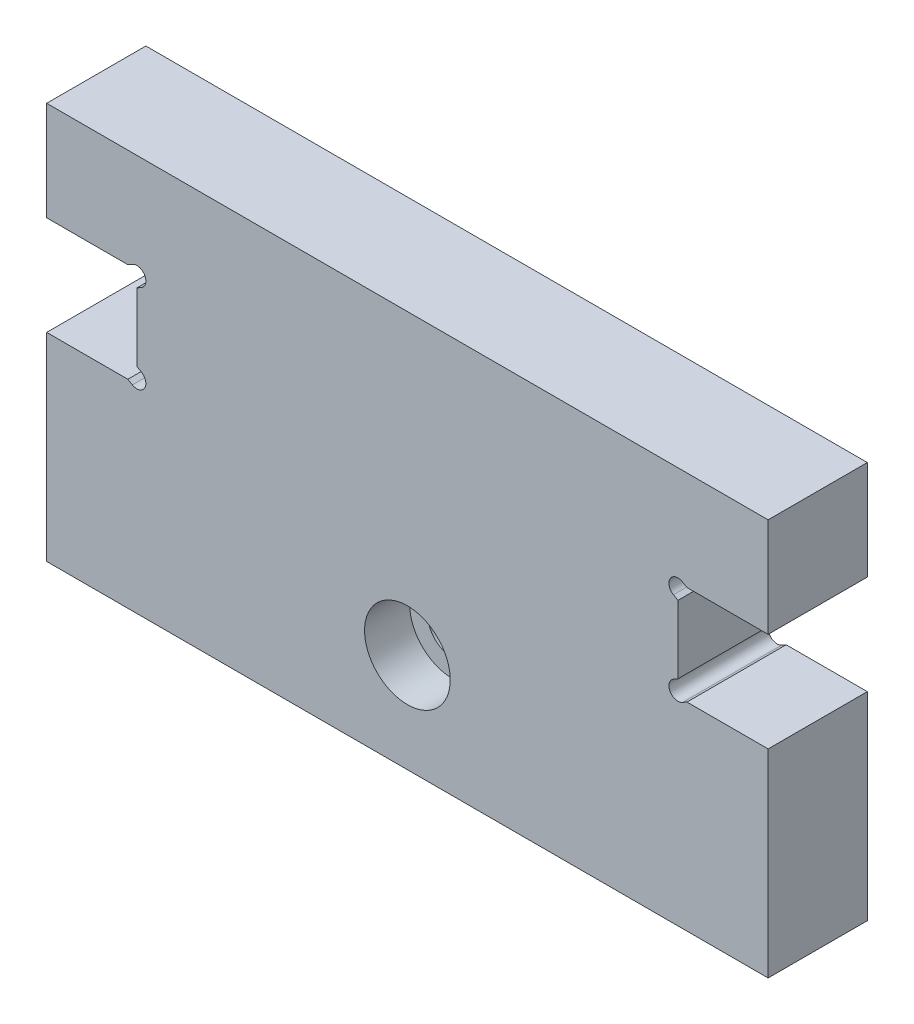
SolidWorks part; units mm, degrees
ref_plane "Piano frontale" through (0, 0, 0) normal (0, 0, 1) x (1, 0, 0)
ref_plane "Piano superiore" through (0, 0, 0) normal (0, 1, 0) x (1, 0, 0)
ref_plane "Piano destro" through (0, 0, 0) normal (1, 0, 0) x (0, 0, -1)
sketch "Profile" plane through (0, 0, 0) normal (0, 0, 1) x (1, 0, 0)
  line L0 (0, 33) -> (9, 33)
  line L1 (0, 0) -> (80, 0)
  line L2 (0, 0) -> (0, 22)
  line L3 (0, 44) -> (80, 44)
  line L5 (10, 31.2679) -> (10, 23.7321)
  line L6 (9, 22) -> (0, 22)
  line L7 (0, 33) -> (0, 44)
  line L8 (40, -17.6134) -> (40, 68.395) construction
  line L9 (9, 22) -> (9.5, 21.7113)
  line L10 (6.6659, 27.5) -> (20.1768, 27.5) construction
  line L11 (10.5, 23.4434) -> (10, 23.7321)
  line L12 (9, 33) -> (9.5, 33.2887)
  line L13 (10.5, 31.5566) -> (10, 31.2679)
  line L14 (73.3341, 27.5) -> (59.8232, 27.5) construction
  line L15 (69.5, 31.5566) -> (70, 31.2679)
  line L16 (71, 33) -> (70.5, 33.2887)
  line L17 (69.5, 23.4434) -> (70, 23.7321)
  line L18 (71, 22) -> (70.5, 21.7113)
  line L19 (80, 33) -> (80, 44)
  line L20 (71, 22) -> (80, 22)
  line L21 (70, 31.2679) -> (70, 23.7321)
  line L22 (80, 0) -> (80, 22)
  line L23 (80, 33) -> (71, 33)
  arc A0 (9.5, 21.7113) -> (10.5, 23.4434) centre (10, 22.5774) ccw
  arc A1 (9.5, 33.2887) -> (10.5, 31.5566) centre (10, 32.4226) cw
  arc A2 (70.5, 33.2887) -> (69.5, 31.5566) centre (70, 32.4226) ccw
  arc A3 (70.5, 21.7113) -> (69.5, 23.4434) centre (70, 22.5774) cw
  point P37 (40, 44)
  point P38 (40, 0)
  dimension "D7" = 2
  dimension "D8" = 10
  dimension "D1" = 40
  dimension "D2" = 44
  dimension "D3" = 11
  dimension "D4" = 22
  dimension "D5" = 30
  dimension "D6" = 1
  dimension "D9" = 30
extrude "Boss-Extrude1" add sketch "Profile" along normal blind 11 contours L3 L19 L23 L16 A2 L15 L21 L17 A3 L18 L20 L22 L1 L2 L6 L9 A0 L11 L5 L13 A1 L12 L0 L7
sketch "Sketch2" plane through (0, 0, 11) normal (0, 0, 1) x (1, 0, 0)
  line L0 (40, -5.088) -> (40, 53.6175) construction
  line L1 (80, 33) -> (80, 44) construction
  line L3 (0, 0) -> (80, 0) construction
  circle A0 centre (40, 11) radius 4.75
  circle A1 centre (40, 11) radius 2.75
  dimension "D2" = 11
  dimension "D1" = 40
extrude "Cut-Extrude1" cut sketch "Sketch2" against normal blind 5 contours A0
extrude "Cut-Extrude2" cut sketch "Sketch2<3>" against normal through all from surface contours A1 starting at face at (44.75, 11, 6)
sketch "Sketch2<3>" plane through (0, 0, 11) normal (0, 0, 1) x (1, 0, 0) same geometry as "Sketch2"
